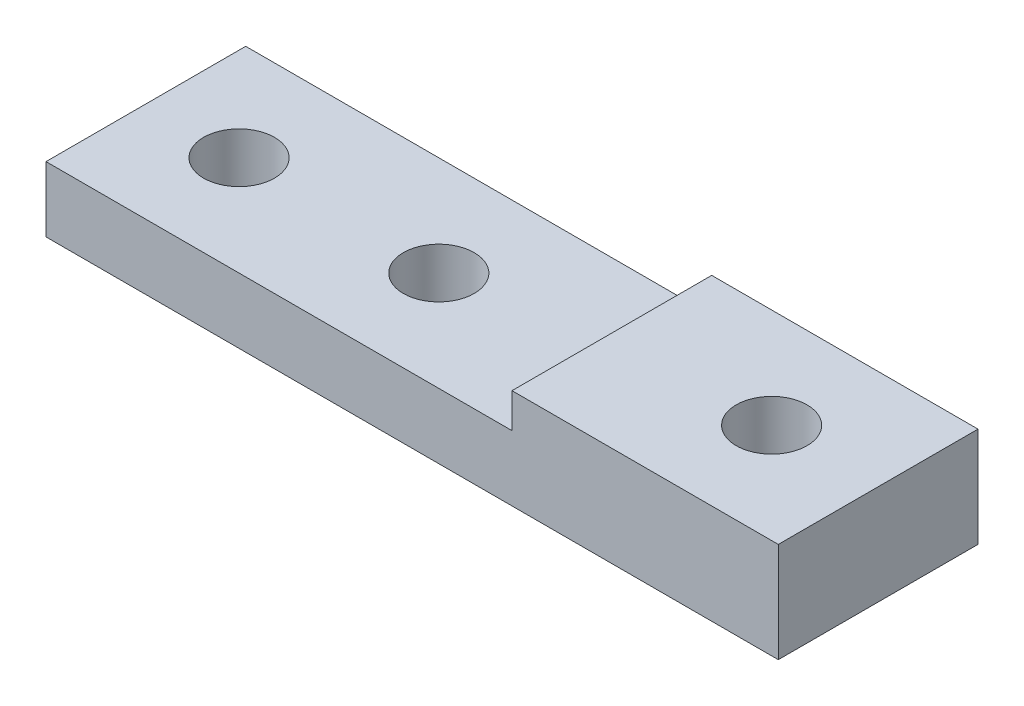
SolidWorks part; units mm, degrees
ref_plane "Front Plane" through (0, 0, 0) normal (0, 0, 1) x (1, 0, 0)
ref_plane "Top Plane" through (0, 0, 0) normal (0, 1, 0) x (1, 0, 0)
ref_plane "Right Plane" through (0, 0, 0) normal (1, 0, 0) x (0, 0, -1)
sketch "Sketch1" plane through (0, 0, 0) normal (0, 1, 0) x (1, 0, 0)
  line L1 (-34.925, 9.525) -> (34.925, 9.525)
  line L2 (-34.925, 9.525) -> (-34.925, -9.525)
  line L3 (-34.925, -9.525) -> (34.925, -9.525)
  line L4 (34.925, 9.525) -> (34.925, -9.525)
  line L5 (-34.925, 9.525) -> (34.925, -9.525) construction
  line L6 (-34.925, -9.525) -> (34.925, 9.525) construction
  point P4 (0, 0)
  point P6 (-6.985, 0)
  point P7 (24.765, 0)
  point P8 (-26.035, 0)
  point P11 (-34.925, 0)
  dimension "D1" = 19.05
  dimension "D2" = 50.8
  dimension "D3" = 19.05
  dimension "D4" = 10.16
  dimension "D5" = 69.85
extrude "Boss-Extrude1" add sketch "Sketch1" along normal blind 6.223
sketch "Sketch4" plane through (0, 6.223, 0) normal (0, 1, 0) x (1, 0, 0)
  line L0 (-34.925, -9.525) -> (34.925, -9.525) construction
  line L1 (34.925, 9.525) -> (9.525, 9.525)
  line L2 (34.925, 9.525) -> (34.925, -9.525)
  line L3 (34.925, -9.525) -> (9.525, -9.525)
  line L4 (9.525, 9.525) -> (9.525, -9.525)
  line L5 (34.925, 9.525) -> (9.525, -9.525) construction
  line L6 (34.925, -9.525) -> (9.525, 9.525) construction
  point P4 (22.225, 0)
  dimension "D1" = 25.4
extrude "Boss-Extrude2" add sketch "Sketch4" along normal blind 3.302
hole_wizard "1/4 Clearance Hole2" positions "Sketch5" profile "Sketch6" hole size "1/4" standard "ANSI Inch" end condition through all
sketch "Sketch5" plane through (0, 0, 0) normal (0, -1, 0) x (-1, 0, 0)
  point P0 (-24.765, 0)
  point P3 (6.985, 0)
  point P6 (26.035, 0)
sketch "Sketch6" plane through (24.765, 0, 0) normal (1, 0, 0) x (0, 0, -1)
  line L0 (0, 0) -> (0, 9.525)
  line L1 (0, 9.525) -> (3.3782, 9.525)
  line L2 (3.3782, 9.525) -> (3.3782, 0)
  line L5 (3.3782, 0) -> (0, 0)
  line L11 (0, -6.35) -> (0, 107.95) construction
  dimension "Thru Hole Dia." = 6.7564
  dimension "Thru Hole Depth" = 9.525
